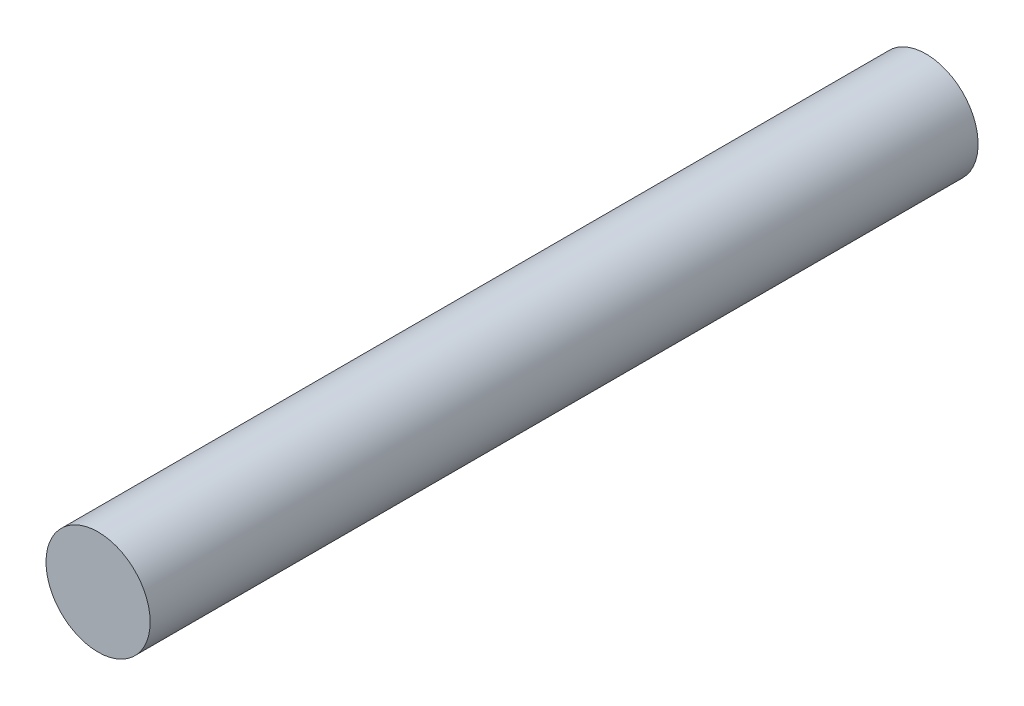
SolidWorks part; units mm, degrees
material "1060 Alloy"
ref_plane "Front Plane" through (0, 0, 0) normal (0, 0, 1) x (1, 0, 0)
ref_plane "Top Plane" through (0, 0, 0) normal (0, 1, 0) x (1, 0, 0)
ref_plane "Right Plane" through (0, 0, 0) normal (1, 0, 0) x (0, 0, -1)
sketch "Sketch1" plane through (0, 0, 0) normal (0, 0, 1) x (1, 0, 0)
  circle A0 centre (0, 0) radius 3
  dimension "D1" = 6
extrude "Boss-Extrude1" add sketch "Sketch1" along normal mid plane 100
sketch "Sketch2" plane through (0, 0, 50) normal (0, 0, 1) x (1, 0, 0)
  circle A1 centre (0, 0) radius 3
  circle A2 centre (0, 0) radius 3
  dimension "D1" = 0
extrude "Cut-Extrude1" cut sketch "Sketch2" against normal up to surface (27.65 mm away)
sketch "Sketch3" plane through (0, 0, -50) normal (0, 0, -1) x (-1, 0, 0)
  circle A1 centre (0, 0) radius 3
  circle A2 centre (0, 0) radius 3
  dimension "D1" = 0
extrude "Cut-Extrude2" cut sketch "Sketch3" against normal offset from surface (24.65 mm away) 3
